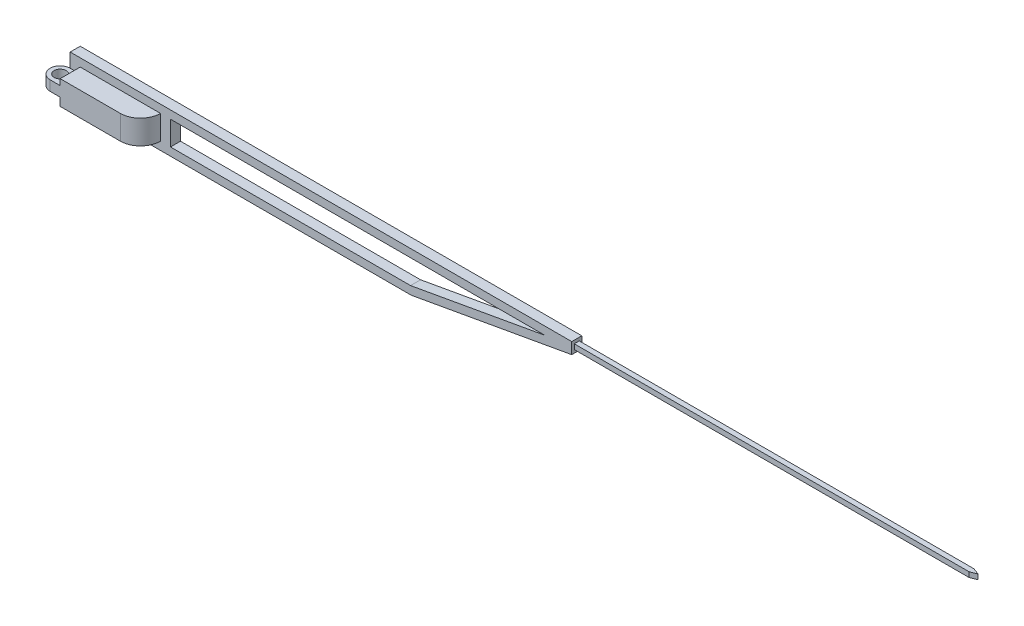
SolidWorks part; units mm, degrees
material "1060 Alloy"
ref_plane "Front" through (0, 0, 0) normal (0, 0, 1) x (1, 0, 0)
ref_plane "Top" through (0, 0, 0) normal (0, 1, 0) x (1, 0, 0)
ref_plane "Right" through (0, 0, 0) normal (1, 0, 0) x (0, 0, -1)
sketch "Sketch1" plane through (0, 0, 0) normal (0, 0, 1) x (1, 0, 0)
  line L0 (0, -2.54) -> (0, 2.54)
  line L1 (0, 2.54) -> (63.5, 2.54)
  line L2 (63.5, 2.54) -> (63.5, 1.101)
  line L3 (63.5, 1.101) -> (43.18, -2.54)
  line L4 (43.18, -2.54) -> (0, -2.54)
  point P2 (0, 0)
  dimension "D1" = 5.08
  dimension "D2" = 63.5
  dimension "D3" = 43.18
  dimension "D4" = 10.159
extrude "Boss-Extrude1" add sketch "Sketch1" along normal mid plane 1.27
sketch "Sketch3" plane through (0, 0, 0) normal (0, 0, 1) x (1, 0, 0)
  line L0 (63.5, 1.8205) -> (114.3, 1.8205)
  line L2 (63.5, 1.101) -> (63.5, 2.54) construction
  dimension "D2" = 50.8
ref_plane "Plane1" through (63.5, 0, 0) normal (1, 0, 0) x (0, 0, -1)
sketch "Sketch4" plane through (63.5, 0, 0) normal (1, 0, 0) x (0, 0, -1)
  line L0 (-0.635, 2.54) -> (0.635, 1.101) construction
  line L5 (-0.3175, 2.138) -> (0.3175, 1.503) construction
  line L6 (-0.635, 1.101) -> (0.635, 2.54) construction
  line L7 (-0.3175, 1.503) -> (0.3175, 1.503)
  line L8 (-0.3175, 1.503) -> (-0.3175, 2.138)
  line L9 (-0.3175, 2.138) -> (0.3175, 2.138)
  line L10 (0.3175, 1.503) -> (0.3175, 2.138)
  line L11 (-0.3175, 1.503) -> (0.3175, 2.138) construction
  point P8 (0, 1.8205)
  point P9 (0, 1.8205)
  dimension "D1" = 0.635
  dimension "D2" = 0.635
sweep "Sweep1" add profiles "Sketch4" path "Sketch3"
sketch "Sketch5" plane through (0, 0, 0.635) normal (0, 0, 1) x (1, 0, 0)
  line L0 (0, 0) -> (12.7, 0) construction
  line L5 (0, 2.54) -> (0, -2.54) construction
  line L18 (12.7, 1.524) -> (12.7, -1.524)
  line L38 (0, -1.524) -> (43.0897, -1.524)
  line L39 (43.0897, -1.524) -> (60.1004, 1.524)
  line L40 (60.1004, 1.524) -> (0, 1.524)
  line L41 (12.7, -1.524) -> (43.0897, -1.524)
  line L42 (43.0897, -1.524) -> (60.1004, 1.524)
  line L43 (60.1004, 1.524) -> (12.7, 1.524)
  dimension "D1" = 12.7
  dimension "D3" = 1.016
extrude "Cut-Extrude2" cut sketch "Sketch5" against normal through all
ref_plane "Plane2" through (0, 0, -0.635) normal (0, 0, -1) x (-1, 0, 0)
sketch "Sketch6" plane through (0, 0, 0.635) normal (0, 0, 1) x (1, 0, 0)
  line L1 (11.43, -1.524) -> (1.27, -1.524)
  line L2 (11.43, -1.524) -> (11.43, 1.524)
  line L3 (11.43, 1.524) -> (1.27, 1.524)
  line L4 (1.27, -1.524) -> (1.27, 1.524)
  line L5 (12.7, -1.524) -> (0, -1.524) construction
  line L6 (0, 2.54) -> (0, -2.54) construction
  line L7 (12.7, 1.524) -> (0, 1.524) construction
  dimension "D1" = 1.27
  dimension "D2" = 10.16
extrude "Boss-Extrude2" add sketch "Sketch6" along normal blind 2.54
fillet "Fillet1" radius 2.54 1 edges at (11.43, 0, 3.175)
ref_plane "Plane3" through (0, 0.127, 0) normal (0, 1, 0) x (1, 0, 0)
sketch "Sketch9" plane through (0, 0.127, 0) normal (0, 1, 0) x (1, 0, 0)
  line L1 (1.27, -0.635) -> (-1.27, -0.635)
  line L2 (1.27, -0.635) -> (1.27, -3.175)
  line L3 (1.27, -3.175) -> (-1.27, -3.175)
  line L4 (-1.27, -0.635) -> (-1.27, -3.175)
  dimension "D1" = 2.54
extrude "Boss-Extrude3" add sketch "Sketch9" along normal mid plane 1.27
sketch "Sketch10" plane through (0, 0.762, 0) normal (0, 1, 0) x (1, 0, 0)
  line L0 (0, -0.635) -> (-1.27, -0.635)
  line L1 (-1.27, -0.635) -> (-1.27, -3.175)
  line L2 (-1.27, -3.175) -> (0, -3.175)
  arc A0 (0, -0.635) -> (0, -3.175) centre (0, -1.905) ccw
  line M3 (0, -0.635) -> (-1.27, -0.635)
  line M4 (-1.27, -0.635) -> (-1.27, -3.175)
  line M5 (-1.27, -3.175) -> (1.27, -3.175)
extrude "Cut-Extrude3" cut sketch "Sketch10" against normal blind 1.27 contours A0 M3 M4 | A0 L1 M5 region at (-0.9863, 0.762, 0.9187) region at (-0.9863, 0.762, 2.8913)
sketch "Sketch11" plane through (0, 0.762, 0) normal (0, 1, 0) x (1, 0, 0)
  circle A0 centre (0, -1.905) radius 0.762
  dimension "D1" = 1.524
extrude "Cut-Extrude4" cut sketch "Sketch11" against normal through all
sketch "Sketch15" plane through (0, 0, -0.635) normal (0, 0, -1) x (-1, 0, 0)
  text T0 "Dave"
extrude "Cut-Extrude5" cut sketch "Sketch15" against normal blind 0.508
sketch "Sketch16" plane through (0, 2.138, 0) normal (0, 1, 0) x (1, 0, 0)
  line L0 (114.3, 0.3175) -> (114.3, -0.3175)
  line L1 (114.3, -0.3175) -> (113.4696, -0.3175)
  line L2 (63.5, -0.3175) -> (114.3, -0.3175) construction
  line L3 (113.4696, -0.3175) -> (114.3, 0)
  line L4 (114.3, 0) -> (113.4696, 0.3175)
  line L5 (63.5, 0.3175) -> (114.3, 0.3175) construction
  line L6 (113.4696, 0.3175) -> (114.3, 0.3175)
  line M3 (63.5, -0.3175) -> (114.3, -0.3175)
  line M4 (114.3, -0.3175) -> (114.3, 0.3175)
  line M5 (114.3, 0.3175) -> (63.5, 0.3175)
  dimension "D1" = 0.889
extrude "Cut-Extrude6" cut sketch "Sketch16" against normal blind 1.27 contours L3 M3 M4 | L4 L0 M5 region at (114.0232, 2.138, 0.2117) region at (114.0232, 2.138, -0.2117)
